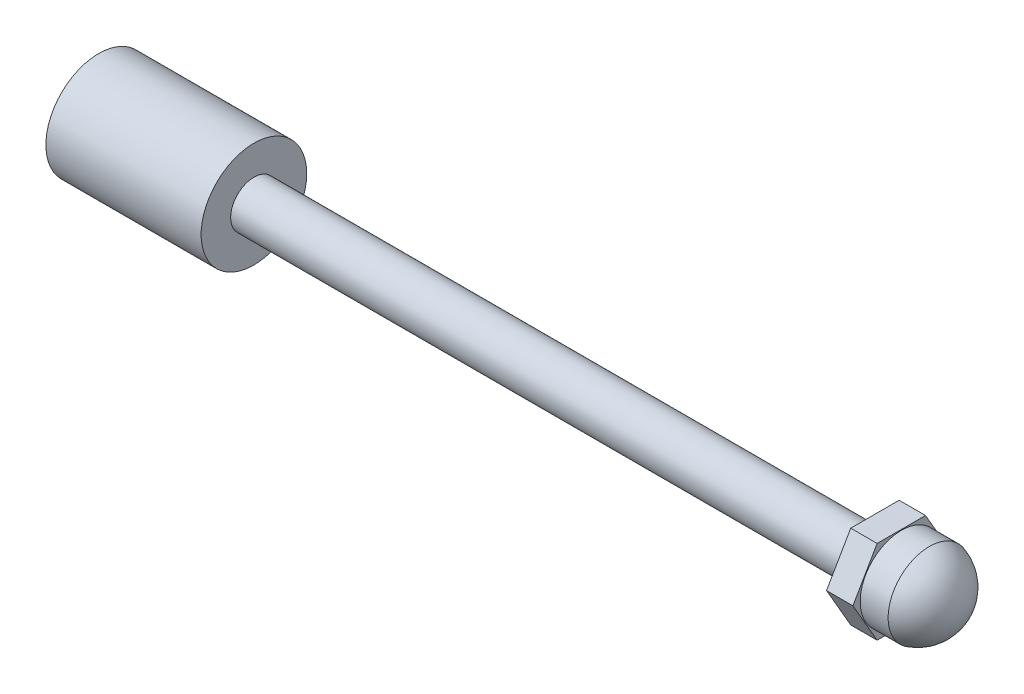
SolidWorks part; units mm, degrees
ref_plane "Front Plane" through (0, 0, 0) normal (0, 0, 1) x (1, 0, 0)
ref_plane "Top Plane" through (0, 0, 0) normal (0, 1, 0) x (1, 0, 0)
ref_plane "Right Plane" through (0, 0, 0) normal (1, 0, 0) x (0, 0, -1)
sketch "Sketch8" plane through (0, 0, 0) normal (1, 0, 0) x (0, 0, -1)
  circle A0 centre (0, 0) radius 3.4
  dimension "D1" = 6.8
extrude "Boss-Extrude1" add sketch "Sketch8" along normal blind 10
sketch "Sketch9" plane through (10, 0, 0) normal (1, 0, 0) x (0, 0, -1)
  circle A0 centre (0, 0) radius 1.5
  dimension "D1" = 3
extrude "Boss-Extrude2" add sketch "Sketch9" along normal blind 40
sketch "Sketch10" plane through (50, 0, 0) normal (1, 0, 0) x (0, 0, -1)
  line L0 (-1.5588, 2.7) -> (1.5588, 2.7)
  line L1 (1.5588, 2.7) -> (3.1177, 0)
  line L2 (3.1177, 0) -> (1.5588, -2.7)
  line L3 (1.5588, -2.7) -> (-1.5588, -2.7)
  line L4 (-1.5588, -2.7) -> (-3.1177, 0)
  line L5 (-3.1177, 0) -> (-1.5588, 2.7)
  line L6 (-1.5588, 2.7) -> (1.5588, -2.7) construction
  circle A1 centre (0, 0) radius 0.8609 construction
  point P7 (0, 0)
extrude "Boss-Extrude3" add sketch "Sketch10" along normal blind 1.7
sketch "Sketch11" plane through (51.7, 0, 0) normal (1, 0, 0) x (0, 0, -1)
  circle A0 centre (0, 0) radius 2.65
  dimension "D1" = 5.3
extrude "Boss-Extrude4" add sketch "Sketch11" along normal blind 1.8
dome "Dome1" faces to dome 1 distance 2 reverse direction no elliptical dome no face at (53.5, 0, -2.65) parameters "D1"=2
ref_plane "Plane1" through (0, 0, 0) normal (0, -0.5, -0.866) x (-1, 0, 0)
